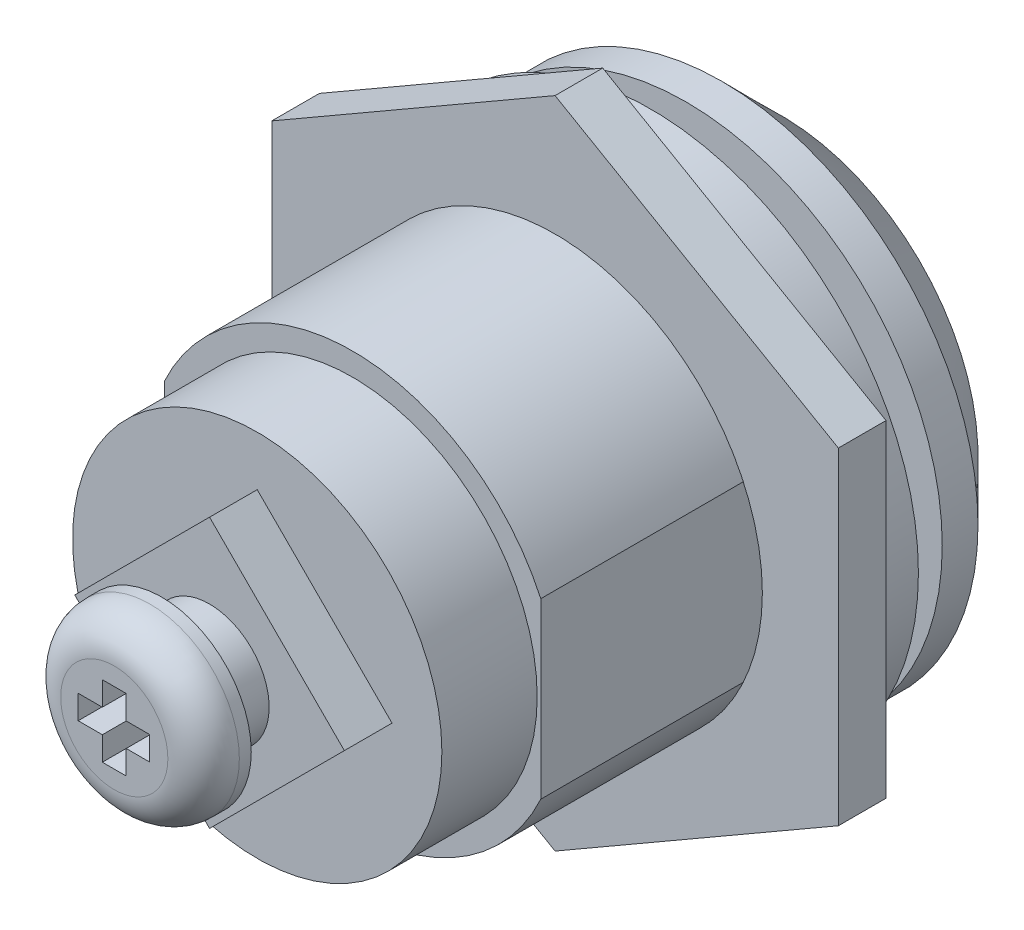
SolidWorks part; units mm, degrees
ref_plane "前视基准面" through (0, 0, 0) normal (0, 0, 1) x (1, 0, 0)
ref_plane "上视基准面" through (0, 0, 0) normal (0, 1, 0) x (1, 0, 0)
ref_plane "右视基准面" through (0, 0, 0) normal (1, 0, 0) x (0, 0, -1)
sketch "草图1" plane through (0, 0, 0) normal (0, 0, 1) x (1, 0, 0)
  line L0 (7.9, 3.6442) -> (7.9, -3.6442)
  line L1 (-7.9, 3.6442) -> (-7.9, -3.6442)
  line L2 (-15.0917, 0) -> (11.0145, 0) construction
  line L3 (0, 12.1407) -> (0, -11.873) construction
  arc A0 (-7.9, -3.6442) -> (7.9, -3.6442) centre (0, 0) ccw
  arc A1 (7.9, 3.6442) -> (-7.9, 3.6442) centre (0, 0) ccw
  dimension "D1" = 8.7
  dimension "D2" = 15.8
extrude "拉伸1_高18低14" add sketch "草图1" along normal blind 18
sketch "草图3" plane through (0, 0, 0) normal (0, 0, -1) x (-1, 0, 0)
  circle A2 centre (0, 0) radius 10.75
  dimension "D1" = 21.5
extrude "拉伸2" add sketch "草图3" along normal blind 4
chamfer "倒角1" distance 2.5 angle 45 1 edges at (-10.75, 0, -4)
ref_plane "基准面2" through (0, 0, 1.5) normal (0, 0, 1) x (1, 0, 0)
sketch "草图4" plane through (0, 0, 1.5) normal (0, 0, 1) x (1, 0, 0)
  line L4 (-7.1166, 3.7625) -> (-7.1166, -3.7625)
  line L5 (7.1166, -3.7625) -> (7.1166, 3.7625)
  arc A1 (-7.1166, -3.7625) -> (7.1166, -3.7625) centre (0, 0) ccw
  arc A2 (7.1166, 3.7625) -> (-7.1166, 3.7625) centre (0, 0) ccw
  circle A6 centre (0, 0) radius 11.25
  circle A7 centre (0, 0) radius 11.25
  dimension "D1" = 0.5
extrude "拉伸3" add sketch "草图4" along normal blind 2
sketch "草图5" plane through (0, 0, 18) normal (0, 0, 1) x (1, 0, 0)
  line L0 (-14.5235, 0) -> (14.0386, 0) construction
  line L1 (0, 12.5838) -> (0, -12.2929) construction
  line L2 (0, 5.6569) -> (-5.6569, 0)
  line L3 (0, 5.6569) -> (5.6569, 0)
  line L4 (0, -5.6569) -> (5.6569, 0)
  line L5 (0, -5.6569) -> (-5.6569, 0)
  dimension "D1" = 8
  dimension "D2" = 45
extrude "拉伸4" add sketch "草图5" along normal blind 2
sketch "草图6" plane through (0, 0, 20) normal (0, 0, 1) x (1, 0, 0)
  line L0 (-9.4803, 0) -> (11.25, 0) construction
  line L1 (0, 7.3466) -> (0, -7.2011) construction
  circle A0 centre (0, 0) radius 11.25 construction
  circle A1 centre (0, 0) radius 2.5
  dimension "D1" = 5
extrude "拉伸5" add sketch "草图6" along normal blind 2
ref_plane "基准面1" through (0, 0, 4.7) normal (0, 0, 1) x (1, 0, 0)
sketch "草图7" plane through (0, 0, 22) normal (0, 0, 1) x (1, 0, 0)
  circle A0 centre (0, 0) radius 3.75
  dimension "D1" = 7.5
extrude "拉伸6" add sketch "草图7" along normal blind 2
fillet "圆角1" radius 1.5 1 edges at (3.75, 0, 24)
sketch "草图8" plane through (0, 0, 24) normal (0, 0, 1) x (1, 0, 0)
  line L0 (-2.7105, 0) -> (2.6865, 0) construction
  line L1 (-1.5147, 0.5) -> (-0.5, 0.5)
  line L2 (-1.5147, 0.5) -> (-1.5147, -0.5)
  line L3 (-1.5147, -0.5) -> (-0.5, -0.5)
  line L4 (1.4853, 0.5) -> (1.4853, -0.5)
  line L5 (-0.5, 1.5) -> (0.5, 1.5)
  line L6 (-0.5, 1.5) -> (-0.5, 0.5)
  line L7 (-0.5, -1.5) -> (0.5, -1.5)
  line L8 (0.5, 1.5) -> (0.5, 0.5)
  line L9 (0, 3.1568) -> (0, -3.2539) construction
  line L10 (0.5, -0.5) -> (0.5, -1.5)
  line L11 (0.5, 0.5) -> (1.4853, 0.5)
  line L12 (-0.5, -0.5) -> (-0.5, -1.5)
  line L13 (0.5, -0.5) -> (1.4853, -0.5)
  dimension "D1" = 1
  dimension "D2" = 1
  dimension "D3" = 3
  dimension "D4" = 3
extrude "切除-拉伸1" cut sketch "草图8" against normal blind 2
sketch "草图9" plane through (0, 0, 3.5) normal (0, 0, 1) x (1, 0, 0)
  line L0 (-23.5872, 0) -> (22.3691, 0) construction
  line L5 (0, 23.4548) -> (0, -20.323) construction
  line L8 (11.8901, -6.8648) -> (0, -13.7295)
  line L9 (-11.8901, -6.8648) -> (-11.8901, 6.8648)
  line L10 (0, 13.7295) -> (11.8901, 6.8648)
  line L11 (11.8901, 6.8648) -> (11.8901, -6.8648)
  line L12 (-11.8901, 6.8648) -> (0, 13.7295)
  line L13 (0, -13.7295) -> (-11.8901, -6.8648)
  circle A3 centre (0, 0) radius 8.7
  dimension "D1" = 17.4
extrude "拉伸7" add sketch "草图9" along normal blind 2
sketch "草图12" plane through (0, 0, -4) normal (0, 0, -1) x (-1, 0, 0)
  circle A0 centre (0, 0) radius 7.25
  dimension "D1" = 14.5
extrude "拉伸8" add sketch "草图12" along normal blind 0.2
fillet "圆角2" radius 0.2 1 edges at (-7.25, 0, -4.2)
sketch "草图10" plane through (0, 0, -4.2) normal (0, 0, -1) x (-1, 0, 0)
  line L0 (0, 8.25) -> (0, -6.9624) construction
  line L2 (-3.5, 1.25) -> (3.5, 1.25)
  line L3 (-3.5, 1.25) -> (-3.5, -1.25)
  line L4 (-3.5, -1.25) -> (3.5, -1.25)
  line L5 (3.5, 1.25) -> (3.5, -1.25)
  line L7 (-5.4732, 0) -> (3.9571, 0) construction
  circle A1 centre (0, 0) radius 8.25 construction
  dimension "D1" = 2.5
  dimension "D2" = 7
extrude "切除-拉伸2" cut sketch "草图10" against normal up to surface (22.2 mm away) up to face at (0, 0, 18)
sketch "草图13" plane through (0, 0, 18) normal (0, 0, 1) x (1, 0, 0)
  line L4 (7.9, -3.6442) -> (7.9, 3.6442)
  line L5 (-7.9, 3.6442) -> (-7.9, -3.6442)
  line L6 (7.9, -3.6442) -> (7.9, 3.6442)
  line L7 (-7.9, 3.6442) -> (-7.9, -3.6442)
  circle A2 centre (0, 0) radius 7.75
  arc A4 (-7.9, -3.6442) -> (7.9, -3.6442) centre (0, 0) ccw
  arc A5 (7.9, 3.6442) -> (-7.9, 3.6442) centre (0, 0) ccw
  arc A6 (-7.9, -3.6442) -> (7.9, -3.6442) centre (0, 0) ccw
  arc A7 (7.9, 3.6442) -> (-7.9, 3.6442) centre (0, 0) ccw
  dimension "D2" = 15.5
  dimension "D1" = 0
extrude "切除-拉伸3" cut sketch "草图13" against normal blind 4
